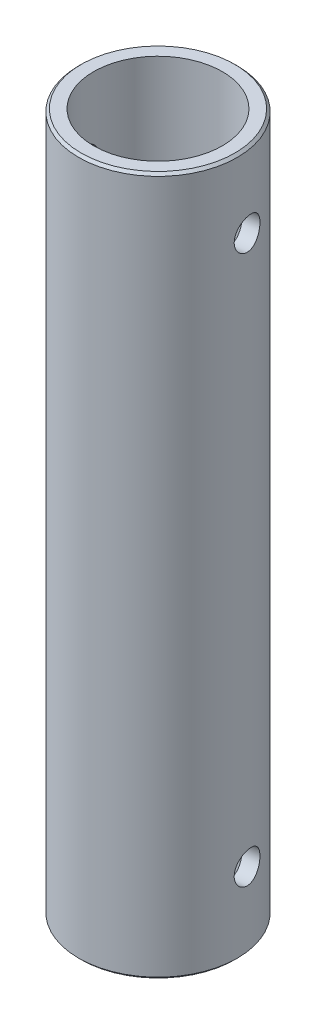
SolidWorks part; units mm, degrees
ref_plane "Front Plane" through (0, 0, 0) normal (0, 0, 1) x (1, 0, 0)
ref_plane "Top Plane" through (0, 0, 0) normal (0, 1, 0) x (1, 0, 0)
ref_plane "Right Plane" through (0, 0, 0) normal (1, 0, 0) x (0, 0, -1)
sketch "Sketch1" plane through (0, 0, 0) normal (0, 1, 0) x (1, 0, 0)
  circle A0 centre (0, 0) radius 7.94
  circle A1 centre (0, 0) radius 6.44
  dimension "D1" = 15.88
  dimension "D2" = 1.5
extrude "Boss-Extrude1" add sketch "Sketch1" along normal blind 69.91
chamfer "Chamfer1" distance 0.25 angle 45 2 edges at (0, 0, 7.94) (0, 69.91, 7.94)
sketch "Sketch2" plane through (-5.7775, 0, 0.9183) normal (-0.9876, 0, 0.157) x (0.157, 0, 0.9876)
  circle A0 centre (0, 7.5) radius 1.55 construction
  circle A1 centre (0, 7.5) radius 1.55
extrude "Cut-Extrude1" cut sketch "Sketch2" against normal through all both and the other way through all
sketch "Sketch3" plane through (-5.7775, 0, 0.9183) normal (-0.9876, 0, 0.157) x (0.157, 0, 0.9876)
  circle A0 centre (0, 62.41) radius 1.55 construction
  circle A1 centre (0, 62.41) radius 1.55
extrude "Cut-Extrude2" cut sketch "Sketch3" against normal through all both and the other way through all
